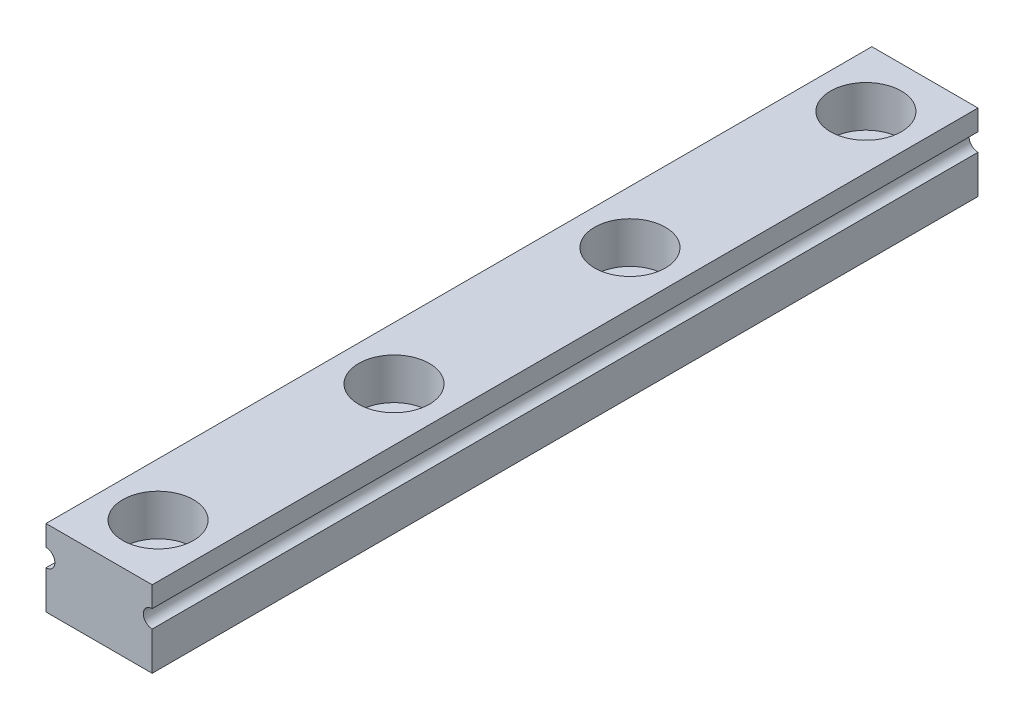
SolidWorks part; units mm, degrees
material "不锈钢 (铁素体)"
ref_plane "前视基准面" through (0, 0, 0) normal (0, 0, 1) x (1, 0, 0)
ref_plane "上视基准面" through (0, 0, 0) normal (0, 1, 0) x (1, 0, 0)
ref_plane "右视基准面" through (0, 0, 0) normal (1, 0, 0) x (0, 0, -1)
sketch "草图1" plane through (0, 0, 0) normal (0, 0, 1) x (1, 0, 0)
  line L1 (0, 0) -> (9, 0)
  line L2 (0, 0) -> (0, 6.5)
  line L3 (0, 6.5) -> (9, 6.5)
  line L4 (9, 0) -> (9, 6.5)
  dimension "D1" = 6.5
  dimension "D2" = 9
extrude "凸台-拉伸1" add sketch "草图1" along normal blind 70
sketch "草图3" plane through (0, 0, 0) normal (0, 0, -1) x (-1, 0, 0)
  line L0 (-9, 4) -> (0, 4) construction
  line L1 (-9, 0) -> (-9, 6.5) construction
  line L2 (0, 6.5) -> (0, 0) construction
  line L4 (0, 0) -> (-9, 0) construction
  circle A0 centre (-9, 4) radius 0.75
  circle A1 centre (0, 4) radius 0.75
  dimension "D2" = 4
  dimension "D1" = 1.5
  dimension "D3" = 1.5
extrude "切除-拉伸2" cut sketch "草图3" against normal through all
sketch "草图2" plane through (0, 6.5, 0) normal (0, 1, 0) x (1, 0, 0)
  line L0 (4.5, 0) -> (4.5, -70) construction
  line L1 (9, 0) -> (0, 0) construction
  line L2 (9, -70) -> (0, -70) construction
  circle A0 centre (4.5, -5) radius 3
  dimension "D1" = 5
  dimension "D2" = 6
extrude "切除-拉伸1" cut sketch "草图2" against normal blind 3.5
sketch "草图4" plane through (0, 6.5, 0) normal (0, 1, 0) x (1, 0, 0)
  circle A0 centre (4.5, -5) radius 1.65
  dimension "D1" = 3.3
extrude "切除-拉伸3" cut sketch "草图4" against normal through all
pattern_linear "阵列(线性)1" count 7 spacing 20 along (0, 0, 1) of "切除-拉伸1", "切除-拉伸3"
